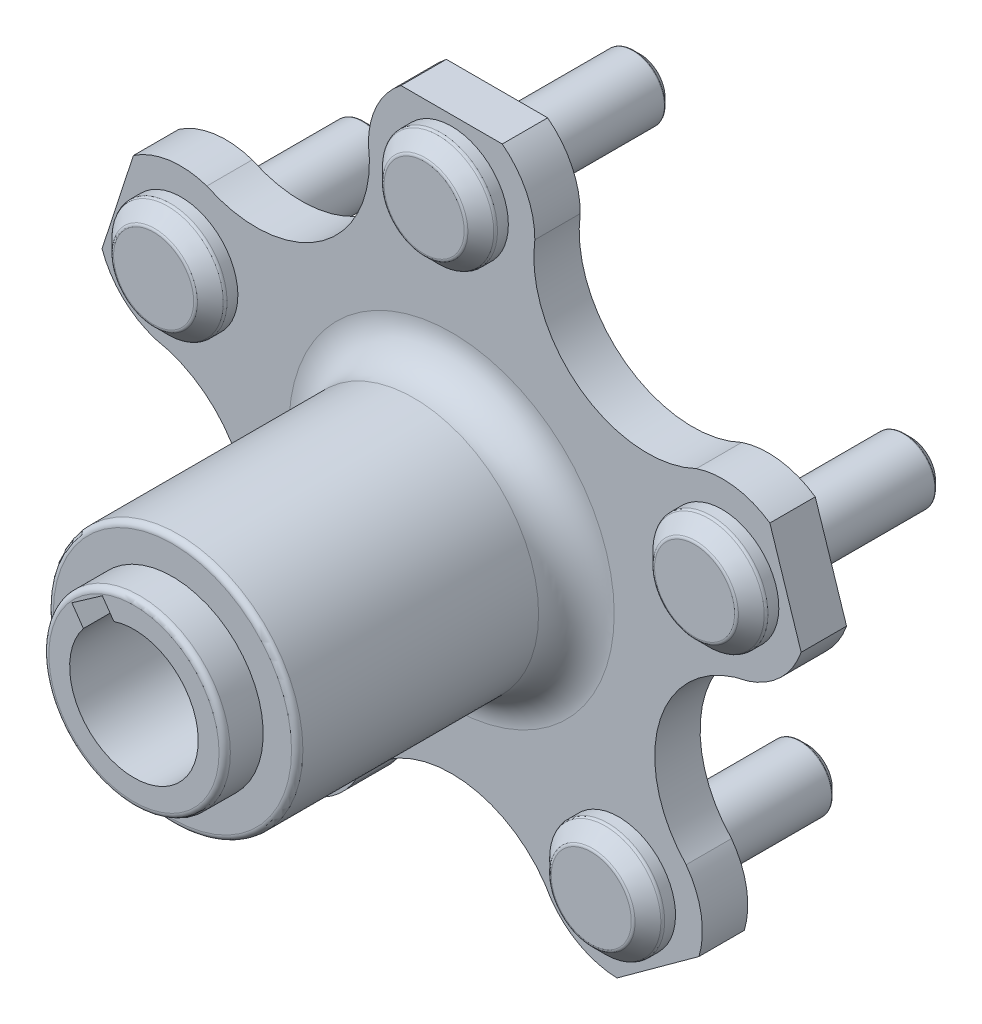
SolidWorks part; units mm, degrees
ref_plane "Front" through (0, 0, 0) normal (0, 0, 1) x (1, 0, 0)
ref_plane "Top" through (0, 0, 0) normal (0, 1, 0) x (1, 0, 0)
ref_plane "Right" through (0, 0, 0) normal (1, 0, 0) x (0, 0, -1)
ref_plane "Plane1" through (0, 0, 0.84) normal (0, 0, 1) x (1, 0, 0)
ref_plane "Plane2" through (0, 0, 6) normal (0, 0, 1) x (1, 0, 0)
ref_axis "Axis1" through (0, 0, 0) along (0, 0, 1)
sketch "Sketch1" plane through (0, 0, 0) normal (0, 0, 1) x (1, 0, 0)
  line L0 (0, 0) -> (0, 27) construction
  line L1 (0, 0) -> (27, 0) construction
  circle A0 centre (0, 0) radius 27 construction
  circle A1 centre (0, 27) radius 4 construction
  circle A2 centre (0, 0) radius 9.6 construction
  circle A3 centre (0, 27) radius 10.1096
  dimension "D1" = 27
sketch "Sketch2" plane through (0, 0, 0) normal (0, 0, 1) x (1, 0, 0)
  line L0 (32.3605, 22.0807) -> (39.1589, 1.1574) construction
  line L1 (0, 0) -> (-46.3069, 15.046) construction
  line L2 (-11, 37.6) -> (11, 37.6) construction
  line L3 (0, 0) -> (46.3069, 15.046) construction
  line L4 (0, 0) -> (28.6193, -39.391) construction
  line L5 (0, 0) -> (-28.6193, -39.391) construction
  line L6 (0, 0) -> (0, 48.69) construction
  line L7 (30.9999, -23.9534) -> (13.2015, -36.8847) construction
  line L8 (-13.2015, -36.8847) -> (-30.9999, -23.9534) construction
  line L9 (-39.1589, 1.1574) -> (-32.3605, 22.0807) construction
  circle A0 centre (0, 0) radius 16.5
  circle A1 centre (0, 37.6) radius 4.2145
  arc A2 (11, 37.6) -> (32.3605, 22.0807) centre (25.8663, 35.602) ccw
  circle A3 centre (35.7597, 11.619) radius 4.2145
  circle A4 centre (22.1007, -30.419) radius 4.2145
  circle A5 centre (-22.1007, -30.419) radius 4.2145
  circle A6 centre (-35.7597, 11.619) radius 4.2145
  arc A7 (39.1589, 1.1574) -> (30.9999, -23.9534) centre (41.8526, -13.5987) ccw
  arc A8 (13.2015, -36.8847) -> (-13.2015, -36.8847) centre (0, -44.0064) ccw
  arc A9 (-30.9999, -23.9534) -> (-39.1589, 1.1574) centre (-41.8526, -13.5987) ccw
  arc A10 (-32.3605, 22.0807) -> (-11, 37.6) centre (-25.8663, 35.602) ccw
  arc A11 (39.1589, 1.1574) -> (32.3605, 22.0807) centre (35.845, 11.6467) ccw
  arc A12 (13.2015, -36.8847) -> (30.9999, -23.9534) centre (22.1534, -30.4916) ccw
  arc A13 (-30.9999, -23.9534) -> (-13.2015, -36.8847) centre (-22.1534, -30.4916) ccw
  arc A14 (-32.3605, 22.0807) -> (-39.1589, 1.1574) centre (-35.845, 11.6467) ccw
  arc A15 (11, 37.6) -> (-11, 37.6) centre (0, 37.6896) ccw
  point P15 (0, 37.6)
  point P25 (0, 0)
  point P33 (0, 0)
  point P44 (0, 0)
  point P54 (0, 0)
  dimension "D1" = 48.69
  dimension "D4" = 5
  dimension "D2" = 5
extrude "Boss-Extrude1" add sketch "Sketch2" along normal blind 6
sketch "Sketch3" plane through (0, 0, 0.84) normal (0, 0, 1) x (1, 0, 0)
  line L3 (-2.6556, 8.0745) -> (-4.1828, 10.2555)
  line L4 (-4.1828, 10.2555) -> (-8.2065, 7.4381)
  line L5 (-6.6793, 5.2571) -> (-8.2065, 7.4381)
  circle A0 centre (0, 0) radius 16.5
  arc A1 (-6.6793, 5.2571) -> (-2.6556, 8.0745) centre (0, 0) ccw
  circle A2 centre (0, 0) radius 12
extrude "Boss-Extrude3" add sketch "Sketch3" along normal blind 42.07 contours A0 A2 | A2 A1 L5 L4 L3 region at (-16.0333, 0, 0.84) region at (-11.6606, 0, 0.84)
extrude "Boss-Extrude4" add sketch "Sketch3<4>" along normal blind 47.16 contours A2 A1 L5 L4 L3 region at (-11.6606, 0, 0.84)
sketch "Sketch3<4>" plane through (0, 0, 0.84) normal (0, 0, 1) x (1, 0, 0) same geometry as "Sketch3"
fillet "Fillet1" radius 5 1 edges at (16.5, 0, 6)
fillet "Fillet2" radius 0.75 1 edges at (16.5, 0, 42.91)
sketch "Sketch4" plane through (0, 0, 0) normal (0, 0, 1) x (1, 0, 0)
  line L0 (46.1125, 25.0051) -> (52.0034, 6.8747)
  line L1 (-9.5317, 46.4174) -> (9.5317, 46.4174)
  line L2 (-9.5317, 46.4174) -> (-9.5317, 51.5826)
  line L3 (-9.5317, 51.5826) -> (9.5317, 51.5826)
  line L4 (9.5317, 46.4174) -> (9.5317, 51.5826)
  line L5 (-9.5317, 46.4174) -> (9.5317, 51.5826) construction
  line L6 (-9.5317, 51.5826) -> (9.5317, 46.4174) construction
  line L7 (47.091, 5.2786) -> (52.0034, 6.8747)
  line L8 (41.2001, 23.409) -> (47.091, 5.2786)
  line L9 (41.2001, 23.409) -> (46.1125, 25.0051)
  line L10 (38.0308, -36.1286) -> (22.6082, -47.3338)
  line L11 (19.5721, -43.1551) -> (22.6082, -47.3338)
  line L12 (34.9948, -31.9499) -> (19.5721, -43.1551)
  line L13 (34.9948, -31.9499) -> (38.0308, -36.1286)
  line L14 (-22.6082, -47.3338) -> (-38.0308, -36.1286)
  line L15 (-34.9948, -31.9499) -> (-38.0308, -36.1286)
  line L16 (-19.5721, -43.1551) -> (-34.9948, -31.9499)
  line L17 (-19.5721, -43.1551) -> (-22.6082, -47.3338)
  line L18 (-52.0034, 6.8747) -> (-46.1125, 25.0051)
  line L19 (-41.2001, 23.409) -> (-46.1125, 25.0051)
  line L20 (-47.091, 5.2786) -> (-41.2001, 23.409)
  line L21 (-47.091, 5.2786) -> (-52.0034, 6.8747)
  line L22 (0, 49) -> (0, 0) construction
  point P0 (0, 49)
  point P23 (0, 0)
  dimension "D1" = 49
extrude "Cut-Extrude1" cut sketch "Sketch4" along normal blind 47.16
fillet "Fillet3" radius 0.75 1 edges at (12, 0, 48)
fillet "Fillet4" radius 1 1 edges at (16.5, 0, 0.84)
sketch "Sketch5" plane through (0, 0, 6) normal (0, 0, 1) x (1, 0, 0)
  circle A0 centre (0, 37.6) radius 7.5
  circle A1 centre (0, 37.6) radius 4.2145
extrude "Boss-Extrude5" add sketch "Sketch5" along normal blind 3.64 separate body contours A0 A1 | A1 region at (-7.2879, 37.6, 6) region at (0, 37.6, 6)
extrude "Boss-Extrude6" add sketch "Sketch5<3>" against normal blind 25 contours A1 region at (0, 37.6, 6)
sketch "Sketch5<3>" plane through (0, 0, 6) normal (0, 0, 1) x (1, 0, 0) same geometry as "Sketch5"
chamfer "Chamfer1" distance 1 angle 45 1 edges at (4.2145, 37.6, -19)
fillet "Fillet6" radius 0.2 2 edges at (4.2145, 37.6, -18) (3.2145, 37.6, -19)
chamfer "Chamfer2" distance 2 angle 45 1 edges at (7.5, 37.6, 9.64)
fillet "Fillet7" radius 0.5 1 edges at (7.5, 37.6, 7.64)
fillet "Fillet8" radius 0.5 1 edges at (5.5, 37.6, 9.64)
pattern_circular "CirPattern1" count 5 over 360 about axis through (0, 0, 0) along (0, 0, 1) of bodies 107
